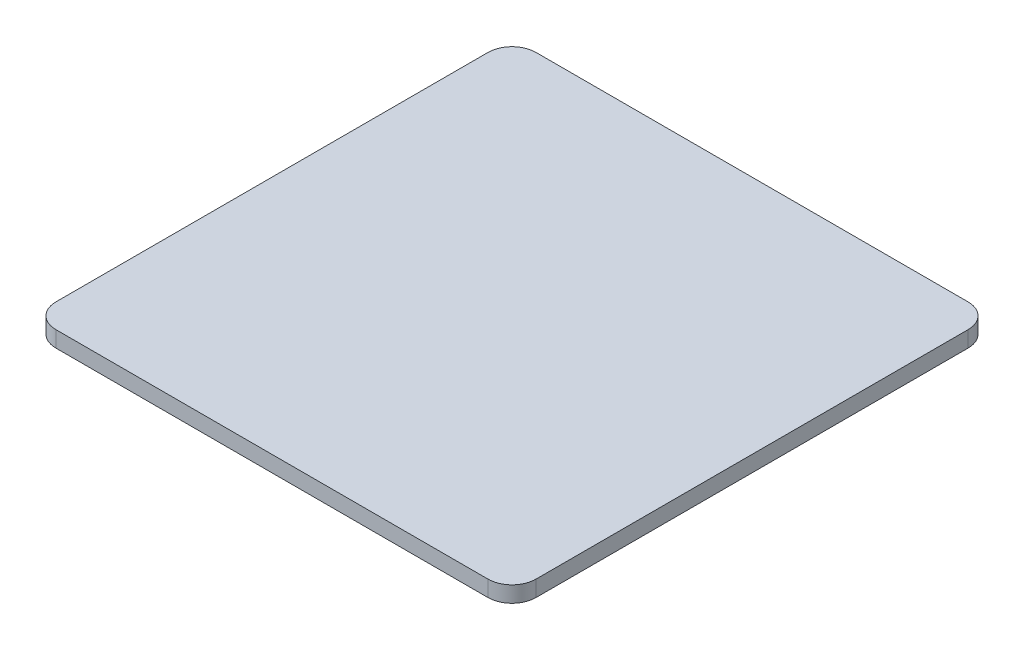
SolidWorks part; units mm, degrees
note: '?' marks a value the reader was unsure of.
material "AISI 304"
ref_plane "Спереди" through (0, 0, 0) normal (0, 0, 1) x (1, 0, 0)
ref_plane "Сверху" through (0, 0, 0) normal (0, 1, 0) x (1, 0, 0)
ref_plane "Справа" through (0, 0, 0) normal (1, 0, 0) x (0, 0, -1)
ref_axis "ОсьX" through (-88.99, 0, 0) along (1, 0, 0)?
ref_axis "ОсьZ" through (0, 55, 0) along (0, -1, 0)?
ref_axis "ОсьY" through (0, 0, -88.99) along (0, 0, 1)?
sketch "Эскиз1" plane through (0, 0, 0) normal (0, 1, 0) x (1, 0, 0)
  line L1 (27, 30) -> (-27, 30)
  line L2 (30, 27) -> (30, -27)
  line L3 (27, -30) -> (-27, -30)
  line L4 (-30, 27) -> (-30, -27)
  line L5 (30, 30) -> (-30, -30) construction
  line L6 (30, -30) -> (-30, 30) construction
  arc A0 (-27, -30) -> (-30, -27) centre (-27, -27) cw
  arc A1 (30, -27) -> (27, -30) centre (27, -27) cw
  arc A2 (27, 30) -> (30, 27) centre (27, 27) cw
  arc A3 (-27, 30) -> (-30, 27) centre (-27, 27) ccw
  point P0 (0, 0)
  dimension "D3" = 3
  dimension "D1" = 60
  dimension "D2" = 60
base flange "Базовая кромка1" sketch "Эскиз1" thickness 2 reverse thickness direction no parameters "D1"=5
sketch "Сгиб-Линии1" plane through (0, 0, 0) normal (0, 1, 0) x (1, 0, 0)
sketch "Граничная рамка1" plane through (0, 0, 0) normal (0, 1, 0) x (1, 0, 0)
sheet metal parameters "Листовой металл9" thickness 2 parameters "D1"=5
flat pattern "Развертка9" [suppressed]
sketch "Сгиб-Линии2" plane through (0, 0, 0) normal (0, 1, 0) x (1, 0, 0)
sketch "Граничная рамка2" [suppressed] plane through (0, 0, 0) normal (0, 1, 0) x (1, 0, 0)
